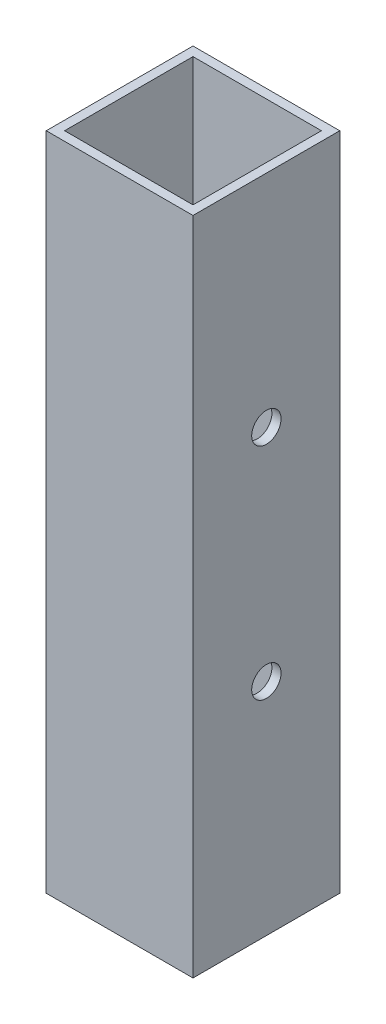
SolidWorks part; units mm, degrees
material "6061 Alloy"
ref_plane "Front Plane" through (0, 0, 0) normal (0, 0, 1) x (1, 0, 0)
ref_plane "Top Plane" through (0, 0, 0) normal (0, 1, 0) x (1, 0, 0)
ref_plane "Right Plane" through (0, 0, 0) normal (1, 0, 0) x (0, 0, -1)
sketch "Sketch1" plane through (0, 0, 0) normal (0, 1, 0) x (1, 0, 0)
  line L1 (12.7, 12.7) -> (-12.7, 12.7)
  line L2 (12.7, 12.7) -> (12.7, -12.7)
  line L3 (12.7, -12.7) -> (-12.7, -12.7)
  line L4 (-12.7, 12.7) -> (-12.7, -12.7)
  line L5 (12.7, 12.7) -> (-12.7, -12.7) construction
  line L6 (12.7, -12.7) -> (-12.7, 12.7) construction
  line L7 (11.1125, 11.1125) -> (-11.1125, 11.1125)
  line L8 (11.1125, 11.1125) -> (11.1125, -11.1125)
  line L9 (11.1125, -11.1125) -> (-11.1125, -11.1125)
  line L10 (-11.1125, 11.1125) -> (-11.1125, -11.1125)
  line L11 (11.1125, 11.1125) -> (-11.1125, -11.1125) construction
  line L12 (11.1125, -11.1125) -> (-11.1125, 11.1125) construction
  point P0 (0, 0)
  point P6 (0, 0)
  dimension "D1" = 25.4
  dimension "D2" = 25.4
  dimension "D3" = 1.5875
  dimension "D4" = 1.5875
extrude "Boss-Extrude1" add sketch "Sketch1" along normal blind 114.3
sketch "Sketch2" plane through (12.7, 0, 0) normal (1, 0, 0) x (0, 0, -1)
  circle A0 centre (0, 73.4511) radius 2.54
  circle A1 centre (0, 41.2276) radius 3.5525
  dimension "D1" = 5.08
sketch "Sketch3" plane through (12.7, 0, 0) normal (1, 0, 0) x (0, 0, -1)
  line L0 (-12.7, 114.3) -> (12.7, 114.3) construction
  line L1 (-12.7, 114.3) -> (-12.7, 0) construction
  line L2 (-12.7, 0) -> (12.7, 0) construction
  circle A0 centre (0, 76.2) radius 2.54
  circle A1 centre (0, 38.1) radius 2.54
  dimension "D1" = 38.1
  dimension "D2" = 12.7
  dimension "D3" = 5.08
  dimension "D4" = 5.08
  dimension "D5" = 12.7
  dimension "D6" = 38.1
extrude "Cut-Extrude1" cut sketch "Sketch3" against normal through all
